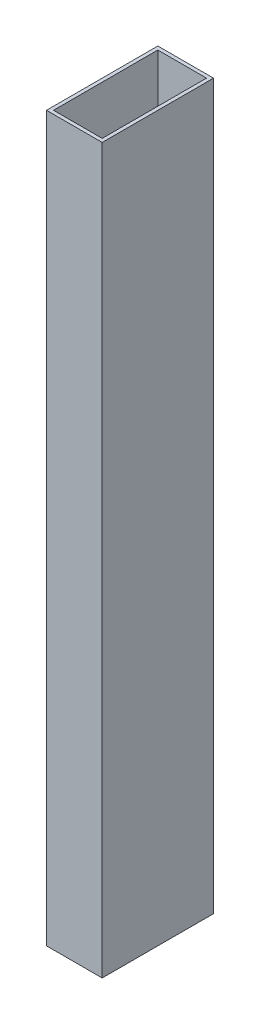
SolidWorks part; units mm, degrees
material "6061-T6 (SS)"
ref_plane "Front" through (0, 0, 0) normal (0, 0, 1) x (1, 0, 0)
ref_plane "Top" through (0, 0, 0) normal (0, 1, 0) x (1, 0, 0)
ref_plane "Right" through (0, 0, 0) normal (1, 0, 0) x (0, 0, -1)
sketch "Sketch1" plane through (0, 0, 0) normal (0, 1, 0) x (1, 0, 0)
  line L1 (12.7, 25.4) -> (-12.7, 25.4)
  line L2 (12.7, 25.4) -> (12.7, -25.4)
  line L3 (12.7, -25.4) -> (-12.7, -25.4)
  line L4 (-12.7, 25.4) -> (-12.7, -25.4)
  line L5 (12.7, 25.4) -> (-12.7, -25.4) construction
  line L6 (12.7, -25.4) -> (-12.7, 25.4) construction
  point P0 (0, 0)
  dimension "D1" = 25.4
  dimension "D2" = 50.8
extrude "Extrude-Thin1" add sketch "Sketch1" along normal up to surface (330.2 mm away) thin thin type one direction reverse wall 1.5875
